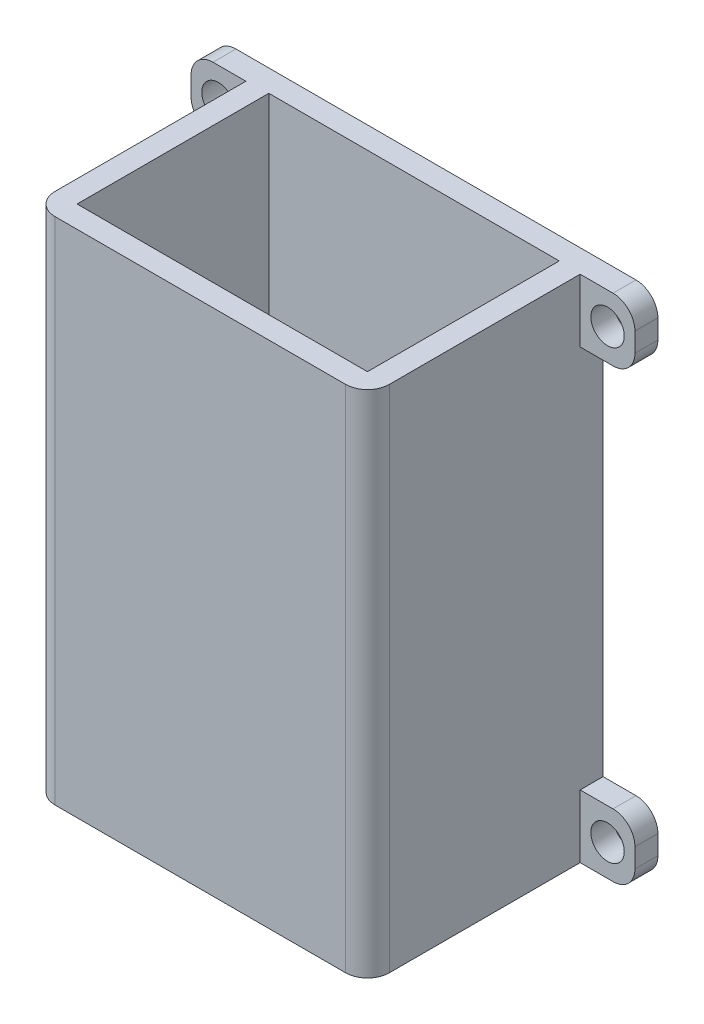
SolidWorks part; units mm, degrees
ref_plane "Front Plane" through (0, 0, 0) normal (0, 0, 1) x (1, 0, 0)
ref_plane "Top Plane" through (0, 0, 0) normal (0, 1, 0) x (1, 0, 0)
ref_plane "Right Plane" through (0, 0, 0) normal (1, 0, 0) x (0, 0, -1)
sketch "Sketch1" plane through (0, 0, 0) normal (0, 1, 0) x (1, 0, 0)
  line L0 (15.25, -10.75) -> (15.25, 10.75)
  line L1 (-13.25, -8.75) -> (13.25, -8.75)
  line L2 (-13.25, -8.75) -> (-13.25, 8.75)
  line L3 (-13.25, 8.75) -> (13.25, 8.75)
  line L4 (13.25, -8.75) -> (13.25, 8.75)
  line L5 (-13.25, -8.75) -> (13.25, 8.75) construction
  line L6 (-13.25, 8.75) -> (13.25, -8.75) construction
  line L7 (-15.25, 10.75) -> (15.25, 10.75)
  line L8 (-15.25, -10.75) -> (-15.25, 10.75)
  line L9 (-15.25, -10.75) -> (15.25, -10.75)
  point P0 (0, 0)
  dimension "D1" = 26.5
  dimension "D2" = 17.5
  dimension "D3" = 2
extrude "Boss-Extrude1" add sketch "Sketch1" along normal blind 46.5
fillet "Fillet1" radius 2 2 edges at (-15.25, 23.25, 10.75) (15.25, 23.25, 10.75)
sketch "Sketch2" plane through (-15.25, 0, 0) normal (-1, 0, 0) x (0, 0, 1)
  line L1 (-10.75, 0) -> (-8.6559, 0)
  line L2 (-10.75, 0) -> (-10.75, 5.7485)
  line L3 (-10.75, 5.7485) -> (-8.6559, 5.7485)
  line L4 (-8.6559, 0) -> (-8.6559, 5.7485)
extrude "Boss-Extrude2" add sketch "Sketch2" along normal blind 5
sketch "Sketch3" plane through (0, 0, -8.6559) normal (0, 0, 1) x (1, 0, 0)
  line L0 (-20.25, 0) -> (-15.25, 0) construction
  line L1 (-17.75, 2.8743) -> (-17.75, 0) construction
  line L2 (-17.75, 0) -> (-17.75, 2.8743) construction
  line L3 (-17.75, 2.8743) -> (-20.25, 2.8743) construction
  line L4 (-20.25, 0) -> (-20.25, 5.7485) construction
  circle A0 centre (-17.75, 2.8743) radius 1.525
  dimension "D1" = 3.05
extrude "Cut-Extrude1" cut sketch "Sketch3" against normal through all both and the other way through all
ref_plane "Plane1" through (0, 23.25, 0) normal (0, 1, 0) x (1, 0, 0)
mirror "Mirror3" about plane through (0, 23.25, 0) normal (0, 1, 0) of "Cut-Extrude1", "Boss-Extrude2"
mirror "Mirror4" about plane through (0, 0, 0) normal (1, 0, 0) of "Mirror3"
fillet "Fillet2" radius 2 8 edges at (20.25, 46.5, -9.7029) (20.25, 40.7515, -9.7029) (20.25, 0, -9.7029) (20.25, 5.7485, -9.7029) (-20.25, 5.7485, -9.7029) (-20.25, 0, -9.7029) (-20.25, 40.7515, -9.7029) (-20.25, 46.5, -9.7029)
